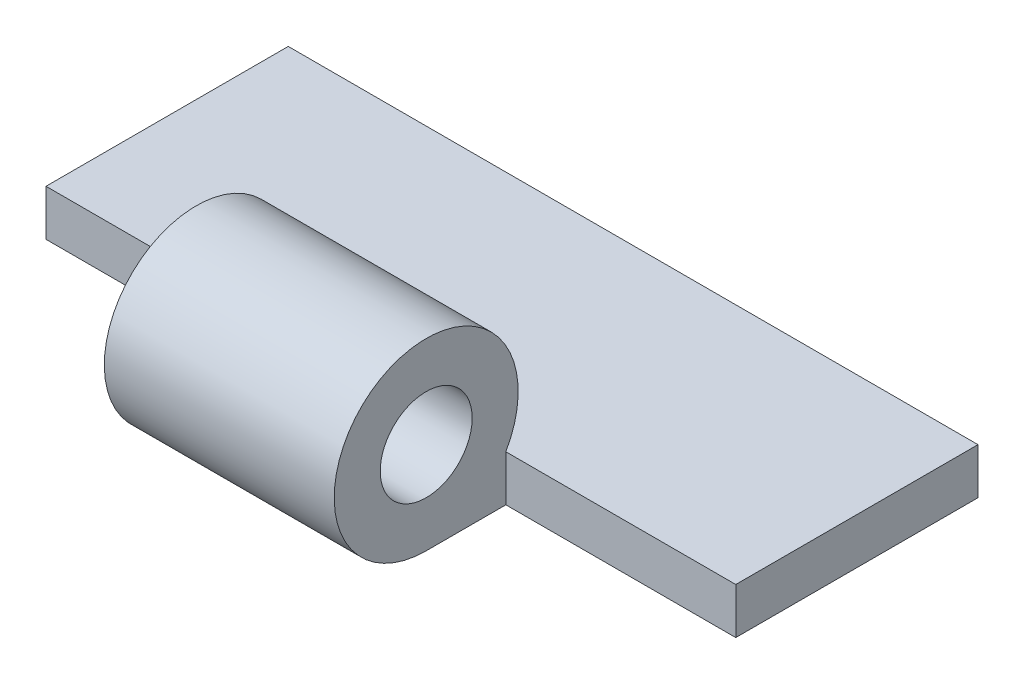
SolidWorks part; units mm, degrees
ref_plane "Ebene vorne" through (0, 0, 0) normal (0, 0, 1) x (1, 0, 0)
ref_plane "Ebene oben" through (0, 0, 0) normal (0, 1, 0) x (1, 0, 0)
ref_plane "Ebene rechts" through (0, 0, 0) normal (1, 0, 0) x (0, 0, -1)
sketch "Skizze1" plane through (0, 0, 0) normal (0, 1, 0) x (1, 0, 0)
  line L1 (0, 0) -> (15, 0)
  line L2 (0, 0) -> (0, 7)
  line L3 (0, 7) -> (15, 7)
  line L4 (15, 0) -> (15, 7)
  dimension "D1" = 15
  dimension "D2" = 7
extrude "Aufsatz-Linear austragen1" add sketch "Skizze1" along normal blind 1
sketch "Skizze2" plane through (15, 0, 0) normal (1, 0, 0) x (0, 0, -1)
  circle A0 centre (0, 2) radius 2
  circle A1 centre (0, 2) radius 1
  dimension "D1" = 2
  dimension "D2" = 1
extrude "Aufsatz-Linear austragen2" add sketch "Skizze2" against normal up to surface (15 mm away) up to face at (0, 0.5, -3.5)
ref_plane "Tangential Ebene" through (0, 0, -2) normal (0, 0, -1) x (-1, 0, 0)
sketch "Skizze8" plane through (15, 0, 0) normal (1, 0, 0) x (0, 0, -1)
  line L0 (1.7321, 1) -> (1.7321, 0)
  line L1 (1.7321, 0) -> (0, 0)
  line L3 (0, 0) -> (7, 0)
  line L4 (7, 0) -> (7, 1)
  line L5 (7, 1) -> (1.7321, 1)
  line L6 (0, 0) -> (7, 0) construction
  line L7 (7, 0) -> (7, 1) construction
  line L8 (7, 1) -> (1.7321, 1) construction
  arc A1 (1.7321, 1) -> (0, 0) centre (0, 2) ccw
  arc A2 (1.7321, 1) -> (0, 0) centre (0, 2) ccw
  dimension "D1" = 0
extrude "Schnitt-Linear austragen1" cut sketch "Skizze8" against normal blind 5
pattern_linear "Lineares Muster1" count 3 spacing 5 along (-1, 0, 0) skipping (1, 0) of "Schnitt-Linear austragen1"
